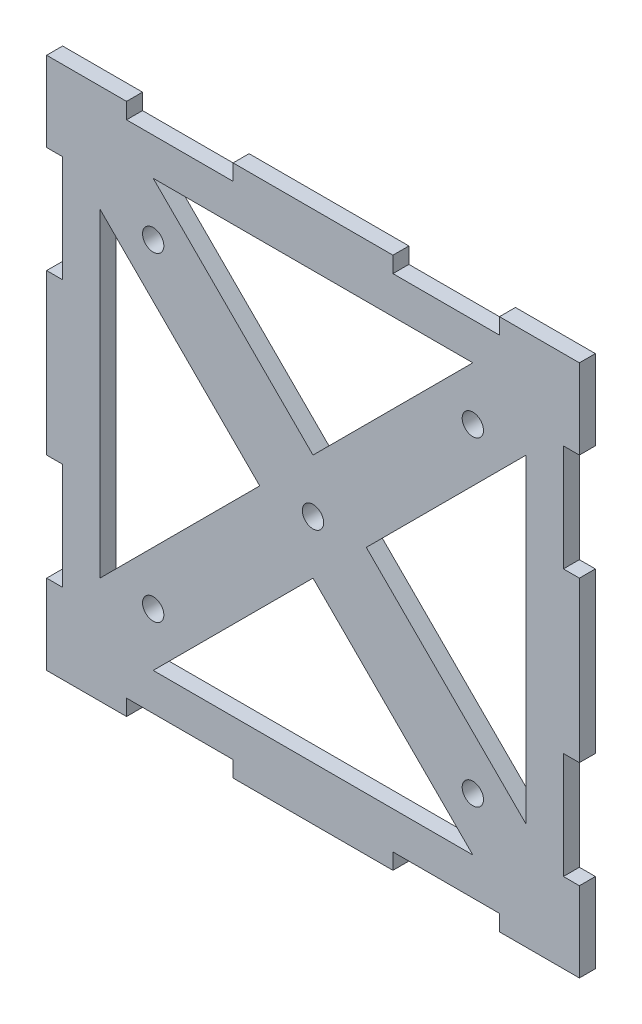
SolidWorks part; units mm, degrees
ref_plane "Plan de face" through (0, 0, 0) normal (0, 0, 1) x (1, 0, 0)
ref_plane "Plan de dessus" through (0, 0, 0) normal (0, 1, 0) x (1, 0, 0)
ref_plane "Plan de droite" through (0, 0, 0) normal (1, 0, 0) x (0, 0, -1)
sketch "Esquisse1" plane through (0, 0, 0) normal (0, 0, 1) x (1, 0, 0)
  line L0 (-36.3514, 95.5523) -> (-36.3514, -4.4477) construction
  line L1 (-86.3514, 103.4275) -> (13.6486, 103.4275)
  line L2 (-86.3514, 103.4275) -> (-86.3514, 3.4275)
  line L3 (-86.3514, 3.4275) -> (13.6486, 3.4275)
  line L4 (13.6486, 103.4275) -> (13.6486, 3.4275)
  line L5 (-76.3514, 93.4275) -> (3.6486, 93.4275)
  line L6 (-76.3514, 93.4275) -> (-76.3514, 13.4275)
  line L7 (-76.3514, 13.4275) -> (3.6486, 13.4275)
  line L8 (3.6486, 93.4275) -> (3.6486, 13.4275)
  line L9 (-94.8547, 53.4275) -> (5.1453, 53.4275) construction
  line L10 (-76.3514, 83.4275) -> (-46.3514, 53.4275)
  line L11 (-66.3514, 93.4275) -> (-36.3514, 63.4275)
  line L12 (-76.3514, 23.4275) -> (-46.3514, 53.4275)
  line L13 (-6.3514, 93.4275) -> (-36.3514, 63.4275)
  line L14 (3.6486, 83.4275) -> (-26.3514, 53.4275)
  line L15 (-66.3514, 13.4275) -> (-36.3514, 43.4275)
  line L16 (-36.3514, 43.4275) -> (-6.3514, 13.4275)
  line L17 (-26.3514, 53.4275) -> (3.6486, 23.4275)
  line L19 (-66.3514, 83.4275) -> (-6.3514, 83.4275) construction
  line L20 (-66.3514, 83.4275) -> (-66.3514, 23.4275) construction
  line L21 (-66.3514, 23.4275) -> (-6.3514, 23.4275) construction
  line L22 (-6.3514, 83.4275) -> (-6.3514, 23.4275) construction
  circle A0 centre (-36.3514, 53.4275) radius 2
  circle A1 centre (-66.3514, 83.4275) radius 2
  circle A2 centre (-6.3514, 83.4275) radius 2
  circle A3 centre (-6.3514, 23.4275) radius 2
  circle A4 centre (-66.3514, 23.4275) radius 2
  point P15 (13.6486, 53.4275)
  point P23 (-36.3514, 3.4275)
  dimension "D25" = 4
  dimension "D26" = 4
  dimension "D27" = 4
  dimension "D28" = 4
  dimension "D29" = 4
  dimension "D1" = 100
  dimension "D2" = 100
  dimension "D3" = 10
  dimension "D4" = 10
  dimension "D5" = 10
  dimension "D6" = 10
  dimension "D7" = 45
  dimension "D8" = 45
  dimension "D9" = 10
  dimension "D10" = 10
  dimension "D11" = 45
  dimension "D12" = 10
  dimension "D13" = 45
  dimension "D14" = 10
  dimension "D15" = 45
  dimension "D16" = 10
  dimension "D17" = 10
  dimension "D18" = 10
  dimension "D19" = 10
  dimension "D20" = 45
  dimension "D21" = 45
  dimension "D22" = 45
  dimension "D23" = 0
  dimension "D24" = 0
extrude "Boss.-Extru.1" add sketch "Esquisse1" along normal blind 3 contours L4 L1 L2 L3 L5 L8 L7 L6 | L17 L14 L8 L5 L13 L11 L6 L10 L12 L7 L15 L16 A4 A3 A2 A1 A0 region at (-36.3514, 102.0132, 0) region at (-71.3514, 92.2961, 0)
sketch "Esquisse2" plane through (0, 0, 3) normal (0, 0, 1) x (1, 0, 0)
  line L0 (-86.3514, 53.4275) -> (13.6486, 53.4275) construction
  line L1 (-86.3514, 103.4275) -> (-86.3514, 3.4275) construction
  line L3 (-36.3514, 103.4275) -> (-36.3514, 3.4275) construction
  line L4 (-86.3514, 103.4275) -> (13.6486, 103.4275) construction
  line L6 (-83.3514, 18.4275) -> (-83.3514, 38.4275)
  line L7 (-71.3514, 103.4275) -> (-51.3514, 103.4275)
  line L8 (-71.3514, 103.4275) -> (-71.3514, 100.4275)
  line L9 (-71.3514, 100.4275) -> (-51.3514, 100.4275)
  line L10 (-51.3514, 103.4275) -> (-51.3514, 100.4275)
  line L11 (-86.3514, 88.4275) -> (-83.3514, 88.4275)
  line L12 (-86.3514, 88.4275) -> (-86.3514, 68.4275)
  line L13 (-86.3514, 68.4275) -> (-83.3514, 68.4275)
  line L14 (-83.3514, 88.4275) -> (-83.3514, 68.4275)
  line L15 (-86.3514, 38.4275) -> (-83.3514, 38.4275)
  line L16 (-86.3514, 18.4275) -> (-86.3514, 38.4275)
  line L17 (-86.3514, 18.4275) -> (-83.3514, 18.4275)
  line L18 (-51.3514, 3.4275) -> (-51.3514, 6.4275)
  line L19 (-71.3514, 6.4275) -> (-51.3514, 6.4275)
  line L20 (-71.3514, 3.4275) -> (-71.3514, 6.4275)
  line L21 (-71.3514, 3.4275) -> (-51.3514, 3.4275)
  line L22 (-1.3514, 3.4275) -> (-21.3514, 3.4275)
  line L23 (-1.3514, 3.4275) -> (-1.3514, 6.4275)
  line L24 (-1.3514, 6.4275) -> (-21.3514, 6.4275)
  line L25 (-21.3514, 3.4275) -> (-21.3514, 6.4275)
  line L26 (13.6486, 18.4275) -> (10.6486, 18.4275)
  line L27 (13.6486, 18.4275) -> (13.6486, 38.4275)
  line L28 (13.6486, 38.4275) -> (10.6486, 38.4275)
  line L29 (10.6486, 88.4275) -> (10.6486, 68.4275)
  line L30 (13.6486, 68.4275) -> (10.6486, 68.4275)
  line L31 (13.6486, 88.4275) -> (13.6486, 68.4275)
  line L32 (13.6486, 88.4275) -> (10.6486, 88.4275)
  line L33 (-21.3514, 103.4275) -> (-21.3514, 100.4275)
  line L34 (-1.3514, 100.4275) -> (-21.3514, 100.4275)
  line L35 (-1.3514, 103.4275) -> (-1.3514, 100.4275)
  line L36 (-1.3514, 103.4275) -> (-21.3514, 103.4275)
  line L37 (10.6486, 18.4275) -> (10.6486, 38.4275)
  point P12 (-86.3514, 53.4275)
  point P13 (-36.3514, 103.4275)
  dimension "D1" = 0
  dimension "D2" = 0
  dimension "D3" = 15
  dimension "D4" = 15
  dimension "D5" = 20
  dimension "D6" = 20
  dimension "D7" = 3
  dimension "D8" = 3
extrude "Enlèv. mat.-Extru.1" cut sketch "Esquisse2" against normal up to next
